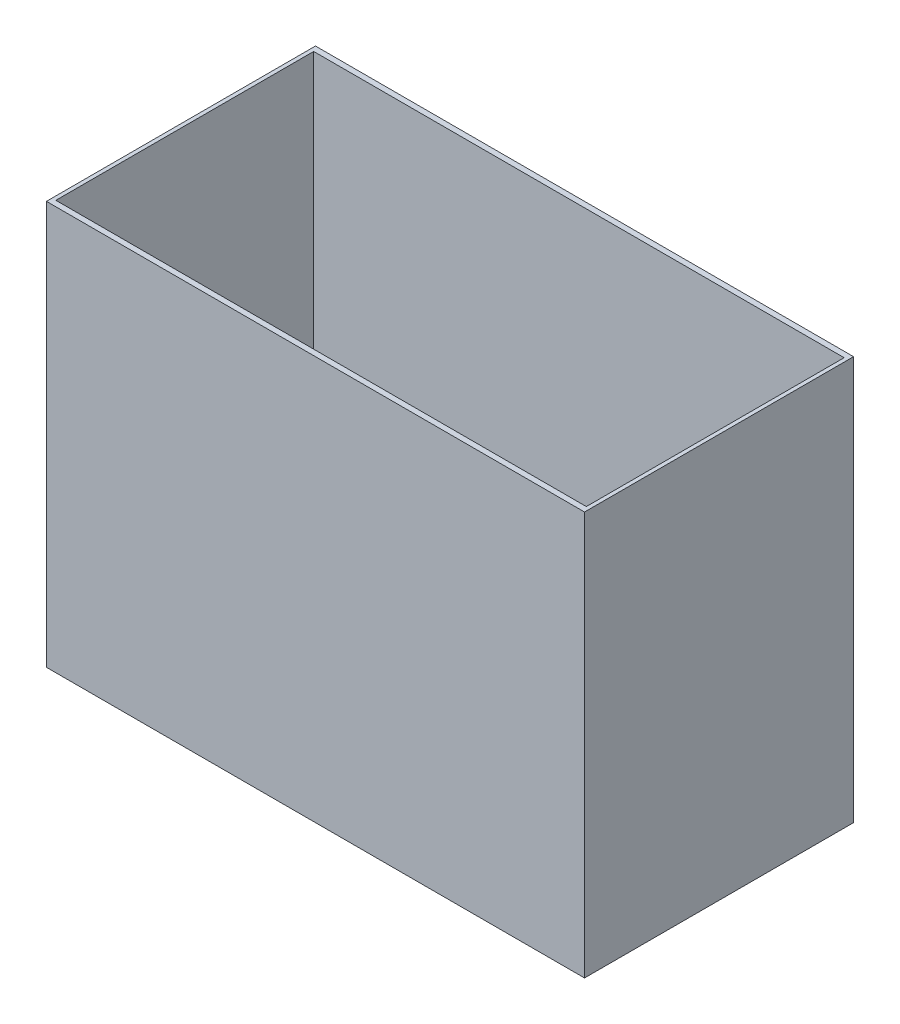
SolidWorks part; units mm, degrees
ref_plane "Front Plane" through (0, 0, 0) normal (0, 0, 1) x (1, 0, 0)
ref_plane "Top Plane" through (0, 0, 0) normal (0, 1, 0) x (1, 0, 0)
ref_plane "Right Plane" through (0, 0, 0) normal (1, 0, 0) x (0, 0, -1)
other "Bounding Box"
ref_plane "Default Plane" through (-292.1, 0, -139.7) normal (0, 1, 0) x (1, 0, 0)
sketch "Sketch1" plane through (0, 0, 0) normal (0, 1, 0) x (1, 0, 0)
  line L0 (-292.1, 0) -> (292.1, 0) construction
  line L1 (-292.1, 139.7) -> (292.1, 139.7)
  line L2 (-292.1, 139.7) -> (-292.1, -139.7)
  line L3 (-292.1, -139.7) -> (292.1, -139.7)
  line L4 (292.1, 139.7) -> (292.1, -139.7)
  line L5 (0, 139.7) -> (0, -139.7) construction
  point P8 (0, 0)
  dimension "D1" = 584.2
  dimension "D2" = 279.4
extrude "Boss-Extrude1" add sketch "Sketch1" along normal blind 12.7
sketch "Sketch2" plane through (0, 12.7, 0) normal (0, 1, 0) x (1, 0, 0)
  line L0 (-245.9259, -63.5) -> (-55.3589, -63.5) construction
  line L1 (-241.3, -120.6497) -> (-152.4, -120.6497)
  line L2 (-241.3, -120.6497) -> (-241.3, -101.5997)
  line L3 (-241.3, -101.5997) -> (-152.4, -101.5997)
  line L4 (-152.4, -120.6497) -> (-152.4, -101.5997)
  line L5 (-241.3, -120.6497) -> (-152.4, -101.5997) construction
  line L6 (-241.3, -101.5997) -> (-152.4, -120.6497) construction
  line L7 (-292.1, 139.7) -> (-292.1, -139.7) construction
  line L8 (-292.1, 0) -> (292.1, 0) construction
  line L9 (292.1, -139.7) -> (292.1, 139.7) construction
  line L10 (0, 0) -> (0, 121.6784) construction
  line L11 (241.3, -101.5997) -> (152.4, -120.6497) construction
  line L12 (241.3, -120.6497) -> (152.4, -101.5997) construction
  line L13 (152.4, -120.6497) -> (152.4, -101.5997)
  line L14 (241.3, -101.5997) -> (152.4, -101.5997)
  line L15 (241.3, -120.6497) -> (241.3, -101.5997)
  line L16 (241.3, -120.6497) -> (152.4, -120.6497)
  point P0 (-196.85, -111.1247)
  point P17 (196.85, -111.1247)
  dimension "D1" = 19.05
  dimension "D2" = 88.9
  dimension "D3" = 38.0997
  dimension "D4" = 50.8
  dimension "D5" = 63.5
extrude "Boss-Extrude2" [suppressed] add sketch "Sketch2" along normal blind 304.8 separate body contours L2 L1 L4 L3
pattern_linear "LPattern1" [suppressed] count 2 spacing 304.8 of bodies 101
pattern_linear "LPattern2" [suppressed] count 2 spacing 215.9 of bodies 101
sketch "Sketch3" plane through (0, 0, 0) normal (0, 1, 0) x (1, 0, 0)
  line L1 (-304.8, -152.4) -> (304.8, -152.4)
  line L2 (-304.8, -152.4) -> (-304.8, 152.4)
  line L3 (-304.8, 152.4) -> (304.8, 152.4)
  line L4 (304.8, -152.4) -> (304.8, 152.4)
  line L5 (-304.8, -152.4) -> (304.8, 152.4) construction
  line L6 (-304.8, 152.4) -> (304.8, -152.4) construction
  line L7 (-300.482, -146.05) -> (300.482, -146.05)
  line L8 (-300.482, -146.05) -> (-300.482, 146.05)
  line L9 (-300.482, 146.05) -> (300.482, 146.05)
  line L10 (300.482, -146.05) -> (300.482, 146.05)
  line L11 (-300.482, -146.05) -> (300.482, 146.05) construction
  line L12 (-300.482, 146.05) -> (300.482, -146.05) construction
  point P0 (0, 0)
  point P6 (0, 0)
  dimension "D1" = 609.6
  dimension "D2" = 304.8
  dimension "D3" = 292.1
  dimension "D4" = 600.964
extrude "Boss-Extrude3" add sketch "Sketch3" along normal blind 457.2 separate body
sketch "Sketch4" plane through (0, 12.7, 0) normal (0, 1, 0) x (1, 0, 0)
  line L0 (292.1, 139.7) -> (-292.1, 139.7) construction
  line L1 (292.1, -139.7) -> (292.1, 139.7) construction
  circle A0 centre (254, 101.6) radius 2.7781
  dimension "D1" = 5.5562
  dimension "D2" = 38.1
  dimension "D3" = 38.1
extrude "Cut-Extrude1" cut sketch "Sketch4" against normal through all
sketch "Sketch6" plane through (0, 0, 0) normal (0, -1, 0) x (1, 0, 0)
  circle A0 centre (254, -101.6) radius 6.35
  circle A1 centre (254, -101.6) radius 2.7781 construction
  dimension "D1" = 12.7
extrude "Cut-Extrude2" cut sketch "Sketch6" against normal blind 2.54
mirror "Mirror1" about plane through (0, 0, 0) normal (0, 0, 1) of "Cut-Extrude2", "Cut-Extrude1"
sketch "Sketch7" plane through (0, 12.7, 0) normal (0, 1, 0) x (1, 0, 0)
  line L0 (292.1, 0) -> (49.4912, 0) construction
  line L1 (292.1, -139.7) -> (292.1, 139.7) construction
  circle A0 centre (190.5, 0) radius 4 construction
  circle A1 centre (190.5, 0) radius 2.7781
  dimension "D1" = 8
  dimension "D2" = 5.5562
  dimension "D3" = 101.6
extrude "Cut-Extrude3" cut sketch "Sketch7" against normal through all
sketch "Sketch8" plane through (0, 12.7, 0) normal (0, 1, 0) x (1, 0, 0)
  circle A0 centre (94.9, -12.8415) radius 1.9844 construction
  circle A1 centre (146.1, -12.8415) radius 1.9844 construction
  circle A2 centre (146.1, 12.8415) radius 1.9844 construction
  circle A3 centre (94.9, 12.8415) radius 1.9844 construction
  circle A4 centre (94.9, -12.8415) radius 1.9844
  circle A5 centre (146.1, -12.8415) radius 1.9844
  circle A6 centre (146.1, 12.8415) radius 1.9844
  circle A7 centre (94.9, 12.8415) radius 1.9844
extrude "Cut-Extrude4" cut sketch "Sketch8" against normal through all
sketch "Sketch9" plane through (0, 0, 0) normal (0, -1, 0) x (1, 0, 0)
  circle A1 centre (190.5, 0) radius 6.35
  circle A2 centre (146.1, 12.8415) radius 6.35
  circle A3 centre (94.9, 12.8415) radius 6.35
  circle A4 centre (94.9, -12.8415) radius 6.35
  circle A5 centre (146.1, -12.8415) radius 6.35
  circle A6 centre (254, 101.6) radius 6.35 construction
extrude "Cut-Extrude5" cut sketch "Sketch9" against normal blind 3.175
